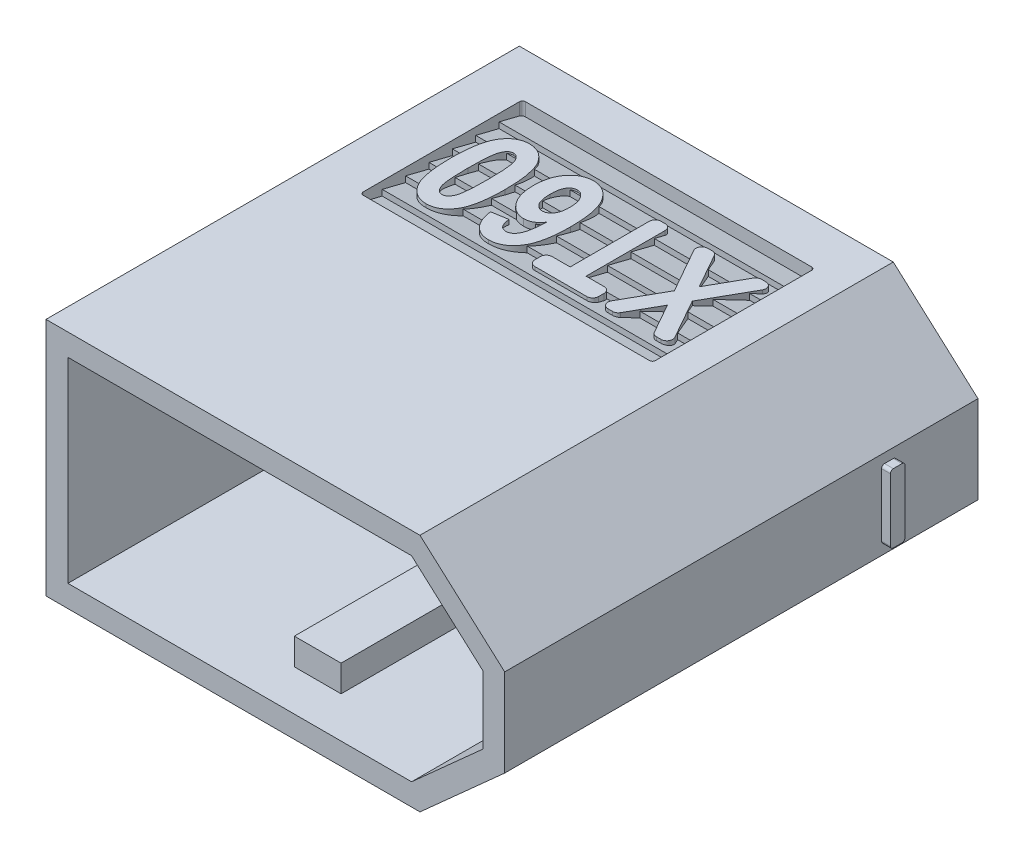
SolidWorks part; units mm, degrees
material "Nylon 101"
ref_plane "Plano frontal" through (0, 0, 0) normal (0, 0, 1) x (1, 0, 0)
ref_plane "Plano superior" through (0, 0, 0) normal (0, 1, 0) x (1, 0, 0)
ref_plane "Plano direito" through (0, 0, 0) normal (1, 0, 0) x (0, 0, -1)
sketch "Esboço1" plane through (0, 0, 0) normal (0, 0, 1) x (1, 0, 0)
  line L0 (0, 0) -> (12.8, 0)
  line L1 (12.8, 0) -> (15.7, 2.6)
  line L2 (15.7, 2.6) -> (15.7, 5.6)
  line L3 (15.7, 5.6) -> (12.8, 8.2)
  line L4 (12.8, 8.2) -> (0, 8.2)
  line L5 (0, 8.2) -> (0, 0)
  dimension "D1" = 12.8
  dimension "D2" = 3
  dimension "D3" = 15.7
  dimension "D4" = 8.2
extrude "Ressalto-extrusão1" add sketch "Esboço1" along normal blind 16.2
sketch "Esboço2" plane through (0, 0, 16.2) normal (0, 0, 1) x (1, 0, 0)
  line L0 (0.75, 7.45) -> (0.75, 0.75)
  line L1 (0.75, 0.75) -> (12.513, 0.75)
  line L2 (12.513, 0.75) -> (14.95, 2.9349)
  line L3 (14.95, 2.9349) -> (14.95, 5.2651)
  line L4 (14.95, 5.2651) -> (12.513, 7.45)
  line L5 (12.513, 7.45) -> (0.75, 7.45)
  line L6 (0, 8.2) -> (0, 0)
  line L7 (0, 0) -> (12.8, 0)
  line L8 (12.8, 0) -> (15.7, 2.6)
  line L9 (15.7, 2.6) -> (15.7, 5.6)
  line L10 (15.7, 5.6) -> (12.8, 8.2)
  line L11 (12.8, 8.2) -> (0, 8.2)
  line L12 (0, 8.2) -> (0, 0) construction
  line L13 (0, 0) -> (12.8, 0) construction
  line L14 (12.8, 0) -> (15.7, 2.6) construction
  line L15 (15.7, 2.6) -> (15.7, 5.6) construction
  line L16 (15.7, 5.6) -> (12.8, 8.2) construction
  line L17 (12.8, 8.2) -> (0, 8.2) construction
  dimension "D1" = 0
  dimension "D2" = 0.75
extrude "Corte-extrusão1" cut sketch "Esboço2" against normal blind 9.4
sketch "Esboço3" plane through (0, 0, 6.8) normal (0, 0, 1) x (1, 0, 0)
  line L1 (7.1, 1.66) -> (8.7, 1.66)
  line L2 (7.1, 1.66) -> (7.1, 0.75)
  line L3 (7.1, 0.75) -> (8.7, 0.75)
  line L4 (8.7, 1.66) -> (8.7, 0.75)
  line L7 (0.75, 0.75) -> (12.513, 0.75) construction
  line L8 (0, 0) -> (12.8, 0) construction
  line L9 (0, 8.2) -> (0, 0) construction
  dimension "D1" = 1.6
  dimension "D2" = 1.66
  dimension "D3" = 8.7
extrude "Ressalto-extrusão2" add sketch "Esboço3" along normal blind 8
sketch "Esboço4" plane through (0, 0, 6.8) normal (0, 0, 1) x (1, 0, 0)
  line L0 (12.513, 7.45) -> (0.75, 7.45) construction
  line L1 (8.7, 1.75) -> (7.1, 1.75)
  line L2 (8.7, 1.75) -> (8.7, 6.45)
  line L3 (8.7, 6.45) -> (7.1, 6.45)
  line L4 (7.1, 1.75) -> (7.1, 6.45)
  line L5 (0.75, 0.75) -> (7.1, 0.75) construction
  line L7 (7.1, 1.66) -> (7.1, 0.75) construction
  line L8 (8.7, 0.75) -> (8.7, 1.66) construction
  dimension "D1" = 1
  dimension "D2" = 1
extrude "Corte-extrusão2" cut sketch "Esboço4" against normal blind 1.5
sketch "Esboço5" plane through (0, 0, 0) normal (0, 0, -1) x (-1, 0, 0)
  line L0 (-15.7, 2.6) -> (-15.7, 5.6) construction
  line L3 (0, 8.2) -> (0, 0) construction
  circle A0 centre (-11.35, 4.1) radius 3
  circle A1 centre (-4.25, 4.1) radius 3
  point P6 (-15.7, 4.1)
  point P9 (-15.7, 4.1)
  dimension "D1" = 6
  dimension "D3" = 4.25
  dimension "D2" = 4.35
extrude "Corte-extrusão3" cut sketch "Esboço5" against normal blind 2
sketch "Esboço6" plane through (0, 0, 2) normal (0, 0, -1) x (-1, 0, 0)
  line L0 (-15.7, 2.6) -> (-15.7, 5.6) construction
  line L3 (0, 8.2) -> (0, 0) construction
  circle A0 centre (-11.35, 4.1) radius 2.15
  circle A2 centre (-4.25, 4.1) radius 2.15
  point P4 (-15.7, 4.1)
  dimension "D1" = 4.3
  dimension "D2" = 6.5
  dimension "D3" = 6.4
extrude "Corte-extrusão4" cut sketch "Esboço6" against normal through all
sketch "Esboço7" plane through (0, 0, 0) normal (-1, 0, 0) x (0, 0, 1)
  line L0 (2.8, 4.35) -> (2.05, 4.35)
  line L1 (4.25, 4.35) -> (3.5, 4.35)
  line L2 (4.35, 4.25) -> (4.35, 3.95)
  line L3 (4.25, 3.85) -> (3.5, 3.85)
  line L4 (1.95, 4.25) -> (1.95, 3.95)
  line L5 (3.3, 5.3) -> (3, 5.3)
  line L6 (3.4, 5.2) -> (3.4, 4.45)
  line L7 (3.3, 2.9) -> (3, 2.9)
  line L8 (2.9, 5.2) -> (2.9, 4.45)
  line L9 (2.8, 3.85) -> (2.05, 3.85)
  line L10 (3.4, 3.75) -> (3.4, 3)
  line L11 (2.9, 3.75) -> (2.9, 3)
  line L12 (0, 8.2) -> (0, 0) construction
  arc A0 (3, 2.9) -> (2.9, 3) centre (3, 3) cw
  arc A1 (3.3, 5.3) -> (3.4, 5.2) centre (3.3, 5.2) cw
  arc A2 (3, 5.3) -> (2.9, 5.2) centre (3, 5.2) ccw
  arc A3 (2.05, 4.35) -> (1.95, 4.25) centre (2.05, 4.25) ccw
  arc A4 (2.05, 3.85) -> (1.95, 3.95) centre (2.05, 3.95) cw
  arc A5 (2.8, 3.85) -> (2.9, 3.75) centre (2.8, 3.75) cw
  arc A6 (2.8, 4.35) -> (2.9, 4.45) centre (2.8, 4.45) ccw
  arc A7 (3.5, 3.85) -> (3.4, 3.75) centre (3.5, 3.75) ccw
  arc A8 (3.4, 3) -> (3.3, 2.9) centre (3.3, 3) cw
  arc A9 (4.35, 3.95) -> (4.25, 3.85) centre (4.25, 3.95) cw
  arc A10 (4.25, 4.35) -> (4.35, 4.25) centre (4.25, 4.25) cw
  arc A11 (3.5, 4.35) -> (3.4, 4.45) centre (3.5, 4.45) cw
  point P12 (1.95, 4.1)
  point P15 (0, 4.1)
  point P28 (2.9, 3.85)
  point P33 (3.4, 3.85)
  point P38 (4.35, 3.85)
  point P41 (4.35, 4.35)
  dimension "D4" = 0.1
  dimension "D1" = 2.4
  dimension "D2" = 0.5
  dimension "D3" = 4.35
extrude "Ressalto-extrusão3" add sketch "Esboço7" along normal blind 0.3
sketch "Esboço8" plane through (15.7, 0, 0) normal (1, 0, 0) x (0, 0, -1)
  line L0 (0, 2.6) -> (0, 5.6) construction
  line L1 (-3.2, 2.925) -> (-2.9, 2.925)
  line L2 (-3.3, 3.025) -> (-3.3, 5.175)
  line L3 (-3.2, 5.275) -> (-2.9, 5.275)
  line L4 (-2.8, 3.025) -> (-2.8, 5.175)
  arc A0 (-3.3, 5.175) -> (-3.2, 5.275) centre (-3.2, 5.175) cw
  arc A1 (-2.9, 5.275) -> (-2.8, 5.175) centre (-2.9, 5.175) cw
  arc A2 (-3.2, 2.925) -> (-3.3, 3.025) centre (-3.2, 3.025) cw
  arc A3 (-2.9, 2.925) -> (-2.8, 3.025) centre (-2.9, 3.025) ccw
  point P4 (-2.8, 4.1)
  point P7 (0, 4.1)
  point P10 (-3.3, 5.275)
  point P13 (-2.8, 5.275)
  point P18 (-2.8, 2.925)
  dimension "D4" = 0.1
  dimension "D1" = 2.35
  dimension "D2" = 0.5
  dimension "D3" = 3.3
extrude "Ressalto-extrusão4" add sketch "Esboço8" along normal blind 0.3
sketch "Esboço9" plane through (0, 0, 0) normal (0, -1, 0) x (1, 0, 0)
  line L0 (12.8, 16.2) -> (12.8, 0) construction
  line L1 (1.75, 7.0931) -> (11.55, 7.0931)
  line L2 (1.65, 6.9931) -> (1.65, 1.6431)
  line L3 (1.75, 1.5431) -> (11.55, 1.5431)
  line L4 (11.65, 6.9931) -> (11.65, 1.6431)
  arc A0 (1.65, 1.6431) -> (1.75, 1.5431) centre (1.75, 1.6431) ccw
  arc A1 (11.55, 1.5431) -> (11.65, 1.6431) centre (11.55, 1.6431) ccw
  arc A2 (11.55, 7.0931) -> (11.65, 6.9931) centre (11.55, 6.9931) cw
  arc A3 (1.75, 7.0931) -> (1.65, 6.9931) centre (1.75, 6.9931) ccw
  dimension "D1" = 0.1
  dimension "D2" = 1.15
  dimension "D3" = 10
  dimension "D4" = 5.55
extrude "Corte-extrusão5" cut sketch "Esboço9" against normal blind 0.75
sketch "Esboço10" plane through (1.65, 0, 0) normal (1, 0, 0) x (0, 0, -1)
  line L0 (-6.8, 0.75) -> (-1.6431, 0.75) construction
  line L1 (-1.5431, 0.75) -> (-1.5431, 0) construction
  line L2 (-3.1431, 0.25) -> (-2.3431, 0.45)
  line L3 (-2.3431, 0.45) -> (-2.3431, 0.25)
  line L5 (-3.1431, 0.45) -> (-3.1431, 0.25)
  line L6 (-2.3431, 0.45) -> (-2.3431, 0.25)
  line L7 (-3.9431, 0.25) -> (-3.1431, 0.45)
  line L8 (-3.9431, 0.45) -> (-3.9431, 0.25)
  line L9 (-4.7431, 0.25) -> (-3.9431, 0.45)
  line L10 (-4.7431, 0.45) -> (-4.7431, 0.25)
  line L11 (-5.5431, 0.25) -> (-4.7431, 0.45)
  line L12 (-5.5431, 0.45) -> (-5.5431, 0.25)
  line L13 (-6.3431, 0.25) -> (-5.5431, 0.45)
  line L14 (-6.3431, 0.45) -> (-6.3431, 0.25)
  line L15 (-7.1431, 0.25) -> (-6.3431, 0.45)
  line L16 (-7.1431, 0.45) -> (-7.1431, 0.25)
  line L17 (-7.1431, 0.45) -> (-7.1431, 0.75)
  line L19 (-2.3431, 0.25) -> (-1.5431, 0.45)
  line L20 (-7.1431, 0.75) -> (-1.5431, 0.75)
  line L21 (-1.5431, 0.45) -> (-1.5431, 0.75)
  line L31 (-2.3431, 0.25) -> (-1.5431, 0.45)
  line M62 (-1.6431, 0) -> (-1.6431, 0.75)
  line M63 (-1.6431, 0.75) -> (-6.8, 0.75)
  line M64 (-6.8, 0.75) -> (-6.9931, 0.75)
  line M65 (-6.9931, 0.75) -> (-6.9931, 0)
  dimension "D1" = 0.8
  dimension "D2" = 0.2
  dimension "D3" = 0.3
  dimension "D4" = 7
extrude "Ressalto-extrusão7" add sketch "Esboço10" along normal up to surface (10 mm away) contours L3 M65 M62 M63 M64 | M62 | M65 region at (1.65, 0.5464, 4.3262) region at (1.65, 0.5937, 1.5938) region at (1.65, 0.5093, 7.0691) up to face at (11.65, 0.45, 4.8145)
ref_plane "Plano1" through (0, 4.1, 0) normal (0, 1, 0) x (1, 0, 0)
mirror "Espelhar1" about plane through (0, 4.1, 0) normal (0, 1, 0) of "Corte-extrusão5", "Ressalto-extrusão7"
ref_plane "Plano2" through (0, 0.5, 0) normal (0, -1, 0) x (-1, 0, 0)
sketch "Esboço11" plane through (0, 0.5, 0) normal (0, -1, 0) x (-1, 0, 0)
  line L1 (-2.131, -7.0931) -> (-2.131, -1.5431) construction
  line L2 (-11.55, -7.0931) -> (-1.75, -7.0931) construction
  line L3 (-11.55, -1.5431) -> (-1.75, -1.5431) construction
  line L4 (-0.85, -6.1831) -> (-0.85, -2.4531) construction
  line L5 (-0.85, -2.4531) -> (-11.65, -2.4531) construction
  line L8 (-11.65, -3.1431) -> (-11.65, -2.3431) construction
  line L10 (-1.65, -6.9931) -> (-1.65, -1.6431) construction
  text T0 "<b><i>TGY</i></b>" font "Calibri" height in points 14
  point P8 (-0.85, -4.3181)
  point P9 (-2.131, -4.3181)
  dimension "D2" = 0.8
  dimension "D1" = 3.73
extrude "Ressalto-extrusão8" add sketch "Esboço11" along normal blind 0.3
ref_plane "Plano3" through (0, 7.7, 0) normal (0, 1, 0) x (1, 0, 0)
sketch "Esboço12" plane through (0, 7.7, 0) normal (0, 1, 0) x (1, 0, 0)
  line L0 (11.0942, -7.0931) -> (11.0942, -1.5431) construction
  line L1 (11.55, -7.0931) -> (1.75, -7.0931) construction
  line L3 (11.3535, -6.0681) -> (11.3535, -2.5681) construction
  line L6 (11.3535, -2.5681) -> (1.9746, -2.5681) construction
  line L7 (11.185, -2.8665) -> (10.3201, -4.3984)
  line L8 (10.3201, -4.3984) -> (11.0942, -5.7698)
  line L9 (10.92, -6.0681) -> (10.7649, -6.0681)
  line L10 (10.5908, -5.9665) -> (10.0126, -4.9431)
  line L11 (10.0126, -4.9431) -> (9.435, -5.9664)
  line L12 (9.2609, -6.0681) -> (9.1051, -6.0681)
  line L13 (8.931, -5.7698) -> (9.705, -4.3984)
  line L14 (9.705, -4.3984) -> (8.8401, -2.8665)
  line L15 (9.0143, -2.5681) -> (9.1699, -2.5681)
  line L16 (9.3441, -2.6698) -> (10.0126, -3.8543)
  line L17 (10.0126, -3.8543) -> (10.6817, -2.6698)
  line L18 (10.8559, -2.5681) -> (11.0109, -2.5681)
  line L19 (7.7626, -2.7681) -> (7.7626, -5.4772)
  line L20 (7.7626, -5.4772) -> (8.3808, -5.4772)
  line L21 (8.5808, -5.6772) -> (8.5808, -5.8681)
  line L22 (8.3808, -6.0681) -> (6.5989, -6.0681)
  line L23 (6.3989, -5.8681) -> (6.3989, -5.6772)
  line L24 (6.5989, -5.4772) -> (7.2171, -5.4772)
  line L25 (7.2171, -5.4772) -> (7.2171, -2.7681)
  line L26 (7.4171, -2.5681) -> (7.5626, -2.5681)
  line L27 (4.2171, -5.2045) -> (4.7626, -5.1136)
  line L28 (11.55, -1.5431) -> (1.75, -1.5431) construction
  arc A0 (7.2171, -2.7681) -> (7.4171, -2.5681) centre (7.4171, -2.7681) cw
  arc A1 (7.7626, -2.7681) -> (7.5626, -2.5681) centre (7.5626, -2.7681) ccw
  arc A2 (6.3989, -5.6772) -> (6.5989, -5.4772) centre (6.5989, -5.6772) cw
  arc A3 (6.5989, -6.0681) -> (6.3989, -5.8681) centre (6.5989, -5.8681) cw
  arc A4 (8.5808, -5.8681) -> (8.3808, -6.0681) centre (8.3808, -5.8681) cw
  arc A5 (8.3808, -5.4772) -> (8.5808, -5.6772) centre (8.3808, -5.6772) cw
  arc A6 (11.185, -2.8665) -> (11.0109, -2.5681) centre (11.0109, -2.7681) ccw
  arc A7 (10.6817, -2.6698) -> (10.8559, -2.5681) centre (10.8559, -2.7681) cw
  arc A8 (9.1699, -2.5681) -> (9.3441, -2.6698) centre (9.1699, -2.7681) cw
  arc A9 (8.8401, -2.8665) -> (9.0143, -2.5681) centre (9.0143, -2.7681) cw
  arc A10 (9.1051, -6.0681) -> (8.931, -5.7698) centre (9.1051, -5.8681) cw
  arc A11 (9.435, -5.9664) -> (9.2609, -6.0681) centre (9.2609, -5.8681) cw
  arc A12 (10.7649, -6.0681) -> (10.5908, -5.9665) centre (10.7649, -5.8681) cw
  arc A13 (11.0942, -5.7698) -> (10.92, -6.0681) centre (10.92, -5.8681) cw
  spline S0 degree 3 poles (4.7626, -5.1136) (4.7682, -5.1739) (4.7813, -5.2594) (4.8192, -5.3612) (4.8534, -5.4198) (4.8944, -5.4666) (4.9618, -5.511) (5.022, -5.5233) (5.0623, -5.5227) knots 0 0 0 0 0.323351 0.457032 0.575726 0.682828 0.785622 1 1 1 1
  spline S1 degree 3 poles (5.0623, -5.5227) (5.09, -5.5233) (5.1312, -5.5165) (5.1832, -5.4965) (5.2201, -5.4751) (5.2548, -5.4474) (5.2873, -5.4137) (5.3188, -5.3744) (5.3485, -5.328) (5.3759, -5.2719) (5.4005, -5.2044) (5.4208, -5.1242) (5.4414, -5.0325) (5.4567, -4.9277) (5.4769, -4.7639) (5.4853, -4.6343) (5.4898, -4.544) knots 0 0 0 0 0.071106 0.106432 0.143035 0.180361 0.220458 0.263402 0.309744 0.362096 0.423824 0.494518 0.575001 0.665718 0.767055 1 1 1 1
  spline S2 degree 3 poles (5.4898, -4.544) (5.4583, -4.5903) (5.407, -4.6546) (5.3276, -4.7255) (5.2671, -4.7681) (5.2028, -4.8002) (5.1126, -4.8326) (5.0401, -4.8399) (4.992, -4.8409) knots 0 0 0 0 0.277998 0.405178 0.526602 0.643637 0.760549 1 1 1 1
  spline S3 degree 3 poles (4.992, -4.8409) (4.9384, -4.84) (4.8576, -4.8324) (4.7559, -4.798) (4.6823, -4.7636) (4.6106, -4.7202) (4.5426, -4.6656) (4.4769, -4.602) (4.4148, -4.529) (4.3577, -4.4481) (4.3074, -4.36) (4.2661, -4.2652) (4.2305, -4.1646) (4.205, -4.0571) (4.1787, -3.9021) (4.1709, -3.7817) (4.1717, -3.6995) knots 0 0 0 0 0.103373 0.154207 0.205955 0.259297 0.315055 0.373347 0.435039 0.499095 0.563542 0.6298 0.697776 0.768574 0.842016 1 1 1 1
  spline S4 degree 3 poles (4.1717, -3.6995) (4.1719, -3.6124) (4.1791, -3.4851) (4.2059, -3.3214) (4.2344, -3.2096) (4.2696, -3.1044) (4.3147, -3.0075) (4.3663, -2.9169) (4.427, -2.8357) (4.4929, -2.7625) (4.5632, -2.698) (4.638, -2.6441) (4.7161, -2.5992) (4.7984, -2.5649) (4.9149, -2.5326) (5.0059, -2.5223) (5.0673, -2.5227) knots 0 0 0 0 0.157847 0.230497 0.300424 0.366636 0.431332 0.493809 0.555163 0.614703 0.672107 0.727719 0.78152 0.834986 0.88891 1 1 1 1
  spline S5 degree 3 poles (5.0673, -2.5227) (5.1348, -2.5224) (5.235, -2.5352) (5.3621, -2.5775) (5.4516, -2.6225) (5.5367, -2.6804) (5.6167, -2.7511) (5.6923, -2.8344) (5.764, -2.9301) (5.8292, -3.0408) (5.8839, -3.1688) (5.9316, -3.3125) (5.969, -3.4733) (5.9997, -3.6502) (6.0283, -3.9192) (6.0353, -4.1298) (6.0353, -4.2755) knots 0 0 0 0 0.090693 0.134685 0.17953 0.224913 0.272738 0.32276 0.375986 0.433204 0.49507 0.562819 0.636478 0.716918 0.804031 1 1 1 1
  spline S6 degree 3 poles (6.0353, -4.2755) (6.0353, -4.4236) (6.0286, -4.6379) (5.9972, -4.9112) (5.9666, -5.0917) (5.9263, -5.2555) (5.8779, -5.4031) (5.8201, -5.5343) (5.7518, -5.6479) (5.6774, -5.7469) (5.5976, -5.8325) (5.5132, -5.906) (5.4224, -5.9645) (5.3276, -6.0115) (5.1918, -6.0556) (5.0843, -6.0686) (5.0119, -6.0681) knots 0 0 0 0 0.192658 0.278521 0.357597 0.430563 0.497753 0.559502 0.616537 0.669747 0.720292 0.768555 0.814847 0.860431 0.905809 1 1 1 1
  spline S7 degree 3 poles (5.0119, -6.0681) (4.9619, -6.0679) (4.888, -6.0616) (4.793, -6.0396) (4.7258, -6.0161) (4.6619, -5.9851) (4.6002, -5.9489) (4.5418, -5.9054) (4.4872, -5.8546) (4.4355, -5.7981) (4.3903, -5.7331) (4.3488, -5.6621) (4.3131, -5.5835) (4.2805, -5.4988) (4.2454, -5.3724) (4.226, -5.2732) (4.2171, -5.2045) knots 0 0 0 0 0.115543 0.170649 0.225187 0.279791 0.334526 0.390474 0.447811 0.50673 0.567186 0.630471 0.696846 0.766493 0.839959 1 1 1 1
  spline S8 degree 3 poles (5.4444, -3.7215) (5.4434, -3.6718) (5.4418, -3.5989) (5.429, -3.5058) (5.4165, -3.4425) (5.399, -3.3843) (5.3797, -3.33) (5.3555, -3.2808) (5.3274, -3.2367) (5.298, -3.1971) (5.2668, -3.1628) (5.2343, -3.1343) (5.2019, -3.1095) (5.1674, -3.0908) (5.1199, -3.0739) (5.0828, -3.0683) (5.058, -3.0681) knots 0 0 0 0 0.178482 0.260709 0.336948 0.409468 0.478213 0.543503 0.605673 0.665087 0.720356 0.771459 0.82001 0.866345 0.91145 1 1 1 1
  spline S9 degree 3 poles (5.058, -3.0681) (5.0113, -3.0673) (4.9398, -3.0858) (4.8626, -3.147) (4.82, -3.1972) (4.7904, -3.2464) (4.7705, -3.2897) (4.7544, -3.3389) (4.7402, -3.3931) (4.7296, -3.4532) (4.7205, -3.5442) (4.7163, -3.6154) (4.7171, -3.6647) knots 0 0 0 0 0.182718 0.277312 0.381921 0.439334 0.501577 0.568146 0.641921 0.72105 0.806868 1 1 1 1
  spline S10 degree 3 poles (4.7171, -3.6647) (4.717, -3.7159) (4.7193, -3.7901) (4.7313, -3.8847) (4.7423, -3.9476) (4.7573, -4.005) (4.7747, -4.0573) (4.7959, -4.1039) (4.8285, -4.1562) (4.8734, -4.2114) (4.9574, -4.2751) (5.0328, -4.2967) (5.0829, -4.2954) knots 0 0 0 0 0.189208 0.273855 0.352112 0.425324 0.492836 0.555472 0.613995 0.720194 0.816437 1 1 1 1
  spline S11 degree 3 poles (5.0829, -4.2954) (5.1315, -4.2955) (5.2057, -4.2763) (5.2877, -4.2147) (5.333, -4.163) (5.3652, -4.1135) (5.3866, -4.0705) (5.4042, -4.0231) (5.4192, -3.9714) (5.4302, -3.915) (5.4422, -3.8316) (5.4445, -3.7663) (5.4444, -3.7215) knots 0 0 0 0 0.192976 0.293261 0.403879 0.464413 0.527516 0.593907 0.665362 0.741186 0.821937 1 1 1 1
  spline S12 degree 3 poles (2.8776, -6.0681) (2.8107, -6.0678) (2.7113, -6.0563) (2.586, -6.0147) (2.4983, -5.9711) (2.4159, -5.915) (2.3386, -5.8466) (2.2662, -5.766) (2.1985, -5.6725) (2.1376, -5.5631) (2.0855, -5.436) (2.0419, -5.2906) (2.0063, -5.1269) (1.978, -4.9448) (1.9513, -4.6654) (1.9446, -4.4461) (1.9444, -4.294) knots 0 0 0 0 0.08972 0.132871 0.17644 0.220536 0.26618 0.314488 0.365396 0.420661 0.481834 0.549191 0.623951 0.706175 0.796104 1 1 1 1
  spline S13 degree 3 poles (1.9444, -4.294) (1.9446, -4.1424) (1.9512, -3.9238) (1.9781, -3.6451) (2.0061, -3.4634) (2.0421, -3.2998) (2.0852, -3.1545) (2.1378, -3.0275) (2.1984, -2.9183) (2.2663, -2.8251) (2.3378, -2.744) (2.4152, -2.6758) (2.4975, -2.6199) (2.5847, -2.5759) (2.7095, -2.5348) (2.8083, -2.5226) (2.8748, -2.5227) knots 0 0 0 0 0.203744 0.29357 0.37599 0.450617 0.518438 0.579462 0.634858 0.685888 0.734097 0.77985 0.824051 0.867439 0.910692 1 1 1 1
  spline S14 degree 3 poles (2.8748, -2.5227) (2.9415, -2.5237) (3.0413, -2.5333) (3.1662, -2.5756) (3.2543, -2.618) (3.3363, -2.6745) (3.4139, -2.742) (3.4862, -2.8219) (3.5413, -2.8978) (3.5827, -2.965) (3.6116, -3.0212) (3.6385, -3.082) (3.6644, -3.1471) (3.6866, -3.2179) (3.708, -3.2929) (3.7271, -3.3725) (3.744, -3.4569) (3.76, -3.5458) (3.7721, -3.64) (3.784, -3.7384) (3.792, -3.842) (3.7994, -3.9499) (3.8057, -4.1036) (3.809, -4.221) (3.808, -4.3011) knots 0 0 0 0 0.089418 0.132451 0.175762 0.219738 0.26505 0.312991 0.363505 0.390209 0.418376 0.447842 0.479108 0.512034 0.546898 0.583358 0.621467 0.661946 0.704107 0.748387 0.794432 0.842956 0.893008 1 1 1 1
  spline S15 degree 3 poles (3.808, -4.3011) (3.8078, -4.4522) (3.8011, -4.6701) (3.7744, -4.9476) (3.7461, -5.1285) (3.7104, -5.2915) (3.6671, -5.4365) (3.6147, -5.5633) (3.554, -5.6725) (3.4861, -5.7657) (3.4146, -5.8468) (3.3372, -5.915) (3.255, -5.9709) (3.1677, -6.0149) (3.0429, -6.056) (2.9441, -6.0682) (2.8776, -6.0681) knots 0 0 0 0 0.203492 0.293171 0.375116 0.449884 0.517528 0.578668 0.634169 0.685295 0.733595 0.779434 0.823719 0.867188 0.910523 1 1 1 1
  spline S16 degree 3 poles (2.8762, -5.5227) (2.9014, -5.5225) (2.9391, -5.5157) (2.9853, -5.4936) (3.0177, -5.4696) (3.0472, -5.4386) (3.0753, -5.4017) (3.1015, -5.3582) (3.1264, -5.3061) (3.1493, -5.2412) (3.1662, -5.1592) (3.1829, -5.0598) (3.1947, -4.9418) (3.2056, -4.806) (3.2148, -4.5879) (3.2172, -4.4152) (3.2171, -4.294) knots 0 0 0 0 0.054972 0.082543 0.111449 0.142586 0.175843 0.2128 0.253578 0.301908 0.362982 0.436475 0.522453 0.622213 0.734739 1 1 1 1
  spline S17 degree 3 poles (3.2171, -4.294) (3.2172, -4.173) (3.2148, -4.0006) (3.2056, -3.7827) (3.1946, -3.6468) (3.1829, -3.5291) (3.1662, -3.4301) (3.1492, -3.3487) (3.1266, -3.2841) (3.1014, -3.2324) (3.0751, -3.189) (3.0477, -3.1515) (3.0174, -3.1212) (2.9854, -3.0972) (2.9391, -3.0752) (2.9014, -3.0683) (2.8762, -3.0681) knots 0 0 0 0 0.265262 0.378009 0.477964 0.564111 0.637236 0.697923 0.746348 0.786738 0.823768 0.857504 0.888332 0.917295 0.944921 1 1 1 1
  spline S18 degree 3 poles (2.8762, -3.0681) (2.8509, -3.0683) (2.8128, -3.0749) (2.7663, -3.0974) (2.7333, -3.1209) (2.7037, -3.1525) (2.675, -3.1892) (2.6497, -3.2336) (2.6244, -3.2852) (2.6028, -3.3503) (2.5854, -3.4315) (2.5689, -3.5305) (2.5569, -3.648) (2.5471, -3.7837) (2.5374, -4.001) (2.5353, -4.1732) (2.5353, -4.294) knots 0 0 0 0 0.055564 0.083174 0.11254 0.143719 0.17775 0.214492 0.255326 0.303553 0.364206 0.437289 0.523386 0.622727 0.735409 1 1 1 1
  spline S19 degree 3 poles (2.5353, -4.294) (2.5354, -4.4152) (2.5374, -4.5879) (2.5471, -4.8059) (2.5568, -4.9419) (2.5689, -5.0598) (2.5854, -5.1593) (2.6027, -5.241) (2.6243, -5.3063) (2.6498, -5.3579) (2.6747, -5.4022) (2.7039, -5.4384) (2.7333, -5.4699) (2.7663, -5.4934) (2.8128, -5.5158) (2.8509, -5.5225) (2.8762, -5.5227) knots 0 0 0 0 0.265055 0.377494 0.477137 0.563048 0.636484 0.697511 0.745634 0.78638 0.823042 0.856591 0.887703 0.917006 0.944556 1 1 1 1
  point P7 (11.0942, -4.3181)
  point P10 (11.3535, -4.3181)
  dimension "D2" = 0.2
  dimension "D1" = 3.5
extrude "Ressalto-extrusão9" add sketch "Esboço12" along normal blind 0.3
